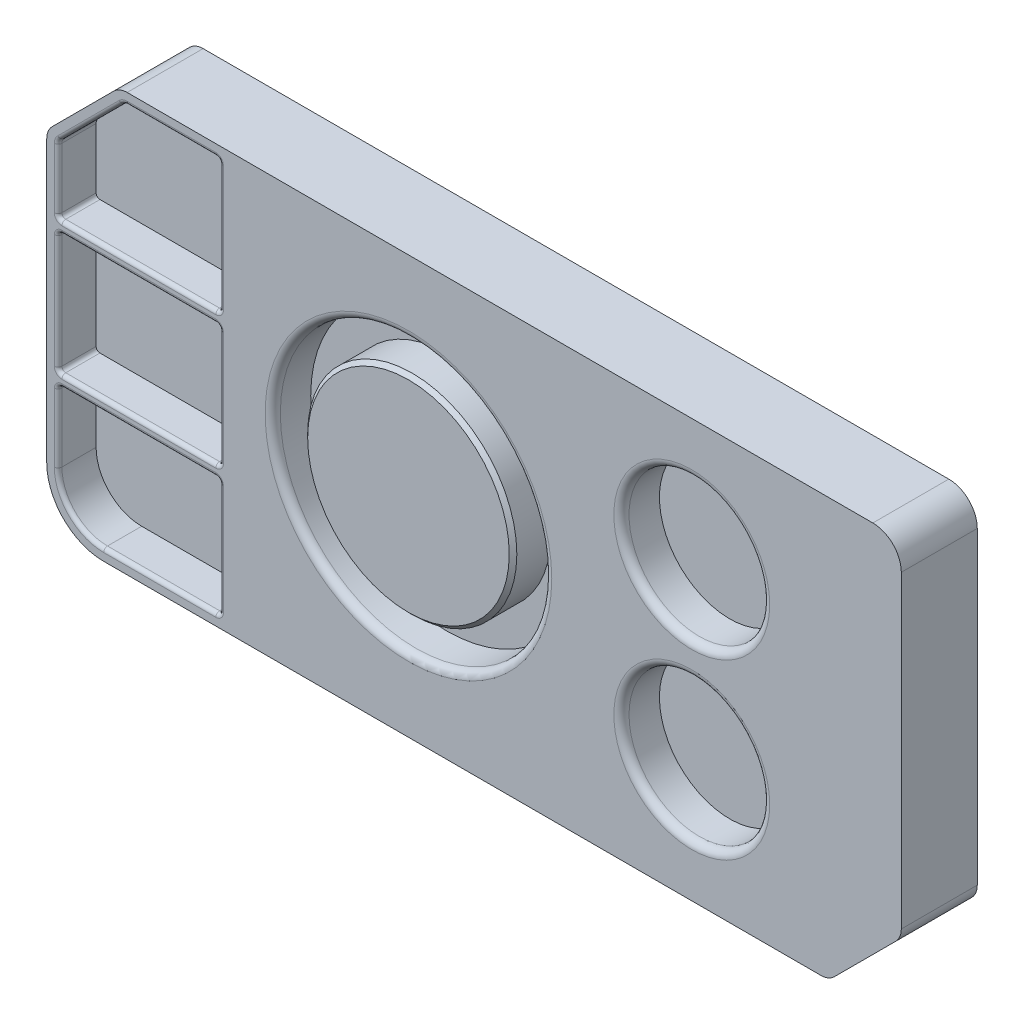
SolidWorks part; units mm, degrees
note: The reader was unsure of these and kept them because the rebuilt part matched: shared geometry of "Sketch4<5>".
material "moto_black"
ref_plane "Front Plane" through (0, 0, 0) normal (0, 0, 1) x (1, 0, 0)
ref_plane "Top Plane" through (0, 0, 0) normal (0, 1, 0) x (1, 0, 0)
ref_plane "Right Plane" through (0, 0, 0) normal (1, 0, 0) x (0, 0, -1)
sketch "Sketch1" plane through (0, 0, 0) normal (0, 0, 1) x (1, 0, 0)
  line L1 (-112.5, -55) -> (112.5, -55)
  line L2 (-112.5, -55) -> (-112.5, 55)
  line L3 (-112.5, 55) -> (112.5, 55)
  line L4 (112.5, -55) -> (112.5, 55)
  line L5 (-112.5, -55) -> (112.5, 55) construction
  line L6 (-112.5, 55) -> (112.5, -55) construction
  point P0 (0, 0)
  dimension "D1" = 225
  dimension "D2" = 110
extrude "Boss-Extrude2" add sketch "Sketch1" along normal blind 10
chamfer "Chamfer1" distance 19.1 angle 45 2 edges at (112.5, -55, 5) (-112.5, 55, 5)
fillet "Fillet1" radius 15 1 edges at (-112.5, -55, 5)
fillet "Fillet2" radius 7.5 1 edges at (112.5, 55, 5)
fillet "Fillet3" radius 5 4 edges at (93.4, -55, 5) (112.5, -35.9, 5) (-112.5, 35.9, 5) (-93.4, 55, 5)
sketch "Sketch4" plane through (0, 0, 10) normal (0, 0, 1) x (1, 0, 0)
  line L6 (105, 55) -> (-91.3289, 55)
  line L7 (-94.8645, 53.5355) -> (-111.0355, 37.3645)
  line L8 (-112.5, 33.8289) -> (-112.5, -40)
  line L9 (-97.5, -55) -> (91.3289, -55)
  line L10 (94.8645, -53.5355) -> (111.0355, -37.3645)
  line L11 (112.5, -33.8289) -> (112.5, 47.5)
  line L12 (-97.5, -52) -> (91.3289, -52)
  line L13 (92.7431, -51.4142) -> (108.9142, -35.2431)
  line L14 (109.5, -33.8289) -> (109.5, 47.5)
  line L15 (105, 52) -> (-91.3289, 52)
  line L16 (-92.7431, 51.4142) -> (-108.9142, 35.2431)
  line L17 (-109.5, 33.8289) -> (-109.5, -40)
  line L18 (-97.5, -52) -> (91.3289, -52)
  line L19 (92.7431, -51.4142) -> (108.9142, -35.2431)
  line L20 (109.5, -33.8289) -> (109.5, 47.5)
  line L21 (105, 52) -> (-91.3289, 52)
  line L22 (-92.7431, 51.4142) -> (-108.9142, 35.2431)
  line L23 (-109.5, 33.8289) -> (-109.5, -40)
  line L24 (-66.9863, 52) -> (-66.9863, -52)
  line L25 (-109.5, 17) -> (-66.9863, 17)
  line L26 (-109.5, -18) -> (-66.9863, -18)
  line L27 (0, 0) -> (-55.0137, 0)
  line L28 (-109.5, 14) -> (-66.9863, 14)
  line L29 (-109.5, -21) -> (-66.9863, -21)
  line L30 (-63.9863, 52) -> (-63.9863, -52)
  arc A6 (-91.3289, 55) -> (-94.8645, 53.5355) centre (-91.3289, 50) ccw
  arc A7 (-111.0355, 37.3645) -> (-112.5, 33.8289) centre (-107.5, 33.8289) ccw
  arc A8 (-112.5, -40) -> (-97.5, -55) centre (-97.5, -40) ccw
  arc A9 (91.3289, -55) -> (94.8645, -53.5355) centre (91.3289, -50) ccw
  arc A10 (111.0355, -37.3645) -> (112.5, -33.8289) centre (107.5, -33.8289) ccw
  arc A11 (112.5, 47.5) -> (105, 55) centre (105, 47.5) ccw
  arc A12 (91.3289, -52) -> (92.7431, -51.4142) centre (91.3289, -50) ccw
  arc A13 (108.9142, -35.2431) -> (109.5, -33.8289) centre (107.5, -33.8289) ccw
  arc A14 (109.5, 47.5) -> (105, 52) centre (105, 47.5) ccw
  arc A15 (-91.3289, 52) -> (-92.7431, 51.4142) centre (-91.3289, 50) ccw
  arc A16 (-108.9142, 35.2431) -> (-109.5, 33.8289) centre (-107.5, 33.8289) ccw
  arc A17 (-109.5, -40) -> (-97.5, -52) centre (-97.5, -40) ccw
  arc A18 (91.3289, -52) -> (92.7431, -51.4142) centre (91.3289, -50) ccw
  arc A19 (108.9142, -35.2431) -> (109.5, -33.8289) centre (107.5, -33.8289) ccw
  arc A20 (109.5, 47.5) -> (105, 52) centre (105, 47.5) ccw
  arc A21 (-91.3289, 52) -> (-92.7431, 51.4142) centre (-91.3289, 50) ccw
  arc A22 (-108.9142, 35.2431) -> (-109.5, 33.8289) centre (-107.5, 33.8289) ccw
  arc A23 (-109.5, -40) -> (-97.5, -52) centre (-97.5, -40) ccw
  circle A24 centre (-17.263, 0) radius 35.7322
  circle A25 centre (57.3334, 22.8052) radius 18.5218
  circle A26 centre (57.3334, -22.8052) radius 18.5218
  circle A27 centre (-17.263, 0) radius 27.5379
  dimension "D3" = 35
  dimension "D4" = 35
  dimension "D1" = 3
  dimension "D2" = 3
  dimension "D5" = 3
  dimension "D6" = 3
extrude "Boss-Extrude4" add sketch "Sketch4" along normal blind 10
fillet "Fillet4" radius 2 3 edges at (75.8552, 22.8052, 20) (75.8552, -22.8052, 20) (18.4692, 0, 20)
extrude "Boss-Extrude5" add sketch "Sketch4<5>" along normal blind 10
sketch "Sketch4<5>" plane through (0, 0, 10) normal (0, 0, 1) x (1, 0, 0) same geometry as "Sketch4"
chamfer "Chamfer2" distance 1 angle 45 1 edges at (10.2749, 0, 20)
fillet "Fillet5" radius 1 3 edges at (-66.9863, -52, 15) (-66.9863, -21, 15) (-109.5, -21, 15)
fillet "Fillet6" radius 1 7 edges at (-109.5, -18, 15) (-109.5, 14, 15) (-66.9863, -18, 15) (-66.9863, 14, 15) (-109.5, 17, 15) (-66.9863, 17, 15) (-66.9863, 52, 15)
fillet "Fillet7" radius 1 26 edges at (-67.2792, -21.2929, 20) (-88.2431, -21, 20) (-109.2071, -21.2929, 20) (-109.5, -31, 20) (-105.9853, -48.4853, 20) (-82.7431, -52, 20) (-67.2792, -51.7071, 20) (-67.2792, 51.7071, 20) (-79.6576, 52, 20) (-92.0943, 51.8478, 20) (-100.8287, 43.3287, 20) (-109.3478, 34.5943, 20) (-109.5, 25.9145, 20) (-109.2071, 17.2929, 20) (-88.2431, 17, 20) (-67.2792, 17.2929, 20) (-67.2792, 13.7071, 20) (-88.2431, 14, 20) (-109.2071, 13.7071, 20) (-109.5, -2, 20) (-109.2071, -17.7071, 20) (-88.2431, -18, 20) (-67.2792, -17.7071, 20) (-66.9863, -36.5, 20) (-66.9863, 34.5, 20) (-66.9863, -2, 20)
